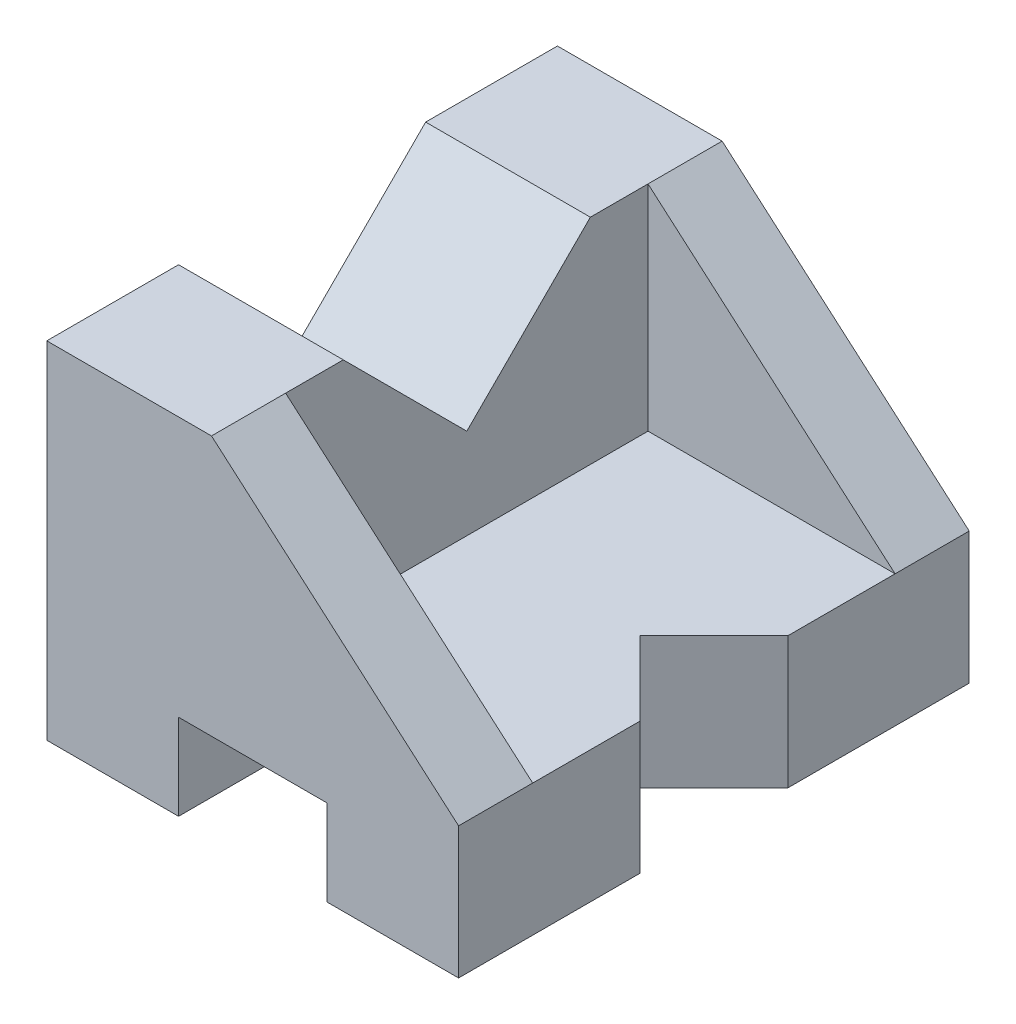
SolidWorks part; units mm, degrees
ref_plane "Front Plane" through (0, 0, 0) normal (0, 0, 1) x (1, 0, 0)
ref_plane "Top Plane" through (0, 0, 0) normal (0, 1, 0) x (1, 0, 0)
ref_plane "Right Plane" through (0, 0, 0) normal (1, 0, 0) x (0, 0, -1)
sketch "Sketch1" plane through (0, 0, 0) normal (0, 0, 1) x (1, 0, 0)
  line L0 (0, 0) -> (16, 0)
  line L1 (16, 0) -> (16, 10.4211)
  line L2 (16, 10.4211) -> (34, 10.4211)
  line L3 (34, 10.4211) -> (34, 0)
  line L4 (34, 0) -> (50, 0)
  line L5 (50, 0) -> (50, 16)
  line L6 (0, 0) -> (0, 42)
  line L7 (0, 42) -> (20, 42)
  line L8 (20, 42) -> (50, 16)
  line L9 (20, 42) -> (20, 16)
  line L10 (20, 16) -> (50, 16)
  dimension "D1" = 42
  dimension "D2" = 16
  dimension "D3" = 16
  dimension "D4" = 18
  dimension "D5" = 16
  dimension "D6" = 20
extrude "Boss-Extrude4" add sketch "Sketch1" along normal mid plane 62 contours L10 L9 L7 L6 L0 L1 L2 L3 L4 L5 region at (18.1121, 18.1051, 0)
extrude "Boss-Extrude5" add sketch "Sketch1<7>" along normal blind 9 from offset 22 contours L9 L10 L8 region at (30, 24.6667, 0)
sketch "Sketch1<7>" plane through (0, 0, 0) normal (0, 0, 1) x (1, 0, 0) same geometry as "Sketch1"
extrude "Boss-Extrude6" add sketch "Sketch1<10>" against normal blind 9 from offset 22 contours L9 L10 L8 region at (30, 24.6667, 0) offset against normal yes
sketch "Sketch1<10>" plane through (0, 0, 0) normal (0, 0, 1) x (1, 0, 0) same geometry as "Sketch1"
sketch "Sketch3" plane through (20, 0, 0) normal (1, 0, 0) x (0, 0, -1)
  line L0 (22, 42) -> (15, 42)
  line L1 (-22, 42) -> (22, 42) construction
  line L2 (15, 42) -> (0, 27)
  line L3 (0, 27) -> (-15, 42)
  line L4 (-15, 42) -> (-22, 42)
  line L5 (-22, 16) -> (22, 16) construction
  line L6 (-15, 42) -> (15, 42)
  point P11 (0, 16)
  line M4 (22, 42) -> (-22, 42)
  dimension "D1" = 7
  dimension "D2" = 7
  dimension "D3" = 15
extrude "Cut-Extrude1" cut sketch "Sketch3" against normal up to next contours L3 L2 M4 region at (20, 37, 0)
sketch "Sketch4" plane through (0, 16, 0) normal (0, 1, 0) x (1, 0, 0)
  line L0 (50, -31) -> (50, -9)
  line L1 (50, -22) -> (50, 22) construction
  line L2 (50, -9) -> (41, 0)
  line L3 (41, 0) -> (50, 9)
  line L4 (50, 9) -> (50, 31)
  line L5 (50, 9) -> (50, -9)
  line M6 (50, -22) -> (50, 22)
  dimension "D1" = 22
  dimension "D2" = 22
  dimension "D3" = 9
extrude "Cut-Extrude2" cut sketch "Sketch4" against normal up to next contours L3 L2 M6 region at (47, 16, 0)
